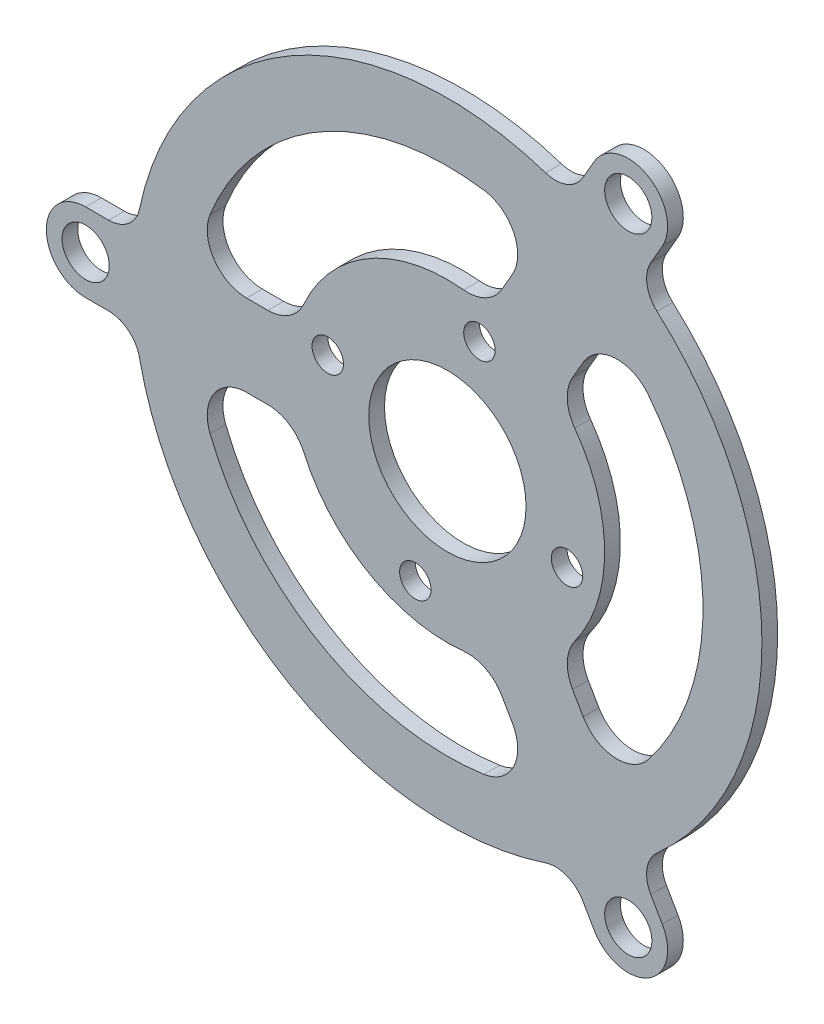
SolidWorks part; units mm, degrees
material "1060 Alloy"
ref_plane "Front Plane" through (0, 0, 0) normal (0, 0, 1) x (1, 0, 0)
ref_plane "Top Plane" through (0, 0, 0) normal (0, 1, 0) x (1, 0, 0)
ref_plane "Right Plane" through (0, 0, 0) normal (1, 0, 0) x (0, 0, -1)
sketch "Sketch1" plane through (0, 0, 0) normal (0, 0, 1) x (1, 0, 0)
  circle A0 centre (0, 0) radius 40
  dimension "D1" = 80
extrude "Boss-Extrude1" add sketch "Sketch1" along normal blind 2
ref_axis "Axis1" through (0, 0, 2) along (0, 0, -1)
sketch "Sketch4" plane through (0, 0, 0) normal (0, 0, -1) x (-1, 0, 0)
  line L0 (0, 0) -> (-40, 0) construction
  line L1 (0, 0) -> (20, 34.641) construction
  line L2 (0, 0) -> (-20, 34.641) construction
  line L3 (-20, 34.641) -> (-23, 39.8372) construction
  line L4 (-18.6699, 42.3372) -> (-15.513, 36.8693)
  line L5 (-27.3301, 37.3372) -> (-24.1733, 31.8693)
  line L6 (-27.3301, 37.3372) -> (-18.6699, 42.3372)
  line L7 (-24.1733, 31.8693) -> (-15.513, 36.8693)
  circle A0 centre (0, 0) radius 40 construction
  circle A1 centre (-23, 39.8372) radius 3
  arc A2 (-18.6699, 42.3372) -> (-27.3301, 37.3372) centre (-23, 39.8372) ccw
  circle M29 centre (0, 0) radius 40
  dimension "D3" = 6
  dimension "D5" = 2
  dimension "D1" = 120
  dimension "D2" = 60
  dimension "D4" = 6
extrude "Boss-Extrude3" add sketch "Sketch4" against normal blind 2 contours A1 L6 L5 L4 M29 | L6 A2 A1 region at (21.2054, 36.7287, 0) region at (19.5958, 41.9408, 0)
fillet "Fillet2" radius 4 2 edges at (24.1733, 31.8693, 1) (15.513, 36.8693, 1)
pattern_circular "CirPattern2" count 3 over 360 about axis through (0, 0, 2) along (0, 0, -1) of "Boss-Extrude3", "Fillet2"
sketch "Sketch5" plane through (0, 0, 0) normal (0, 0, -1) x (-1, 0, 0)
  circle A0 centre (0, 0) radius 10
  dimension "D1" = 20
extrude "Cut-Extrude1" cut sketch "Sketch5" against normal blind 8
sketch "Sketch6" plane through (0, 0, 0) normal (0, 0, -1) x (-1, 0, 0)
  line L0 (0, 0) -> (20, 0) construction
  line L1 (0, 0) -> (4.0764, -15.2133) construction
  line L2 (0, 0) -> (-14.8462, -25.7143) construction
  circle A0 centre (4.0764, -15.2133) radius 2
  circle A1 centre (0, 0) radius 20 construction
  dimension "D3" = 4
  dimension "D4" = 40
  dimension "D1" = 45
  dimension "D2" = 15.75
  dimension "D5" = 120
sketch "Sketch7" plane through (0, 0, 0) normal (0, 0, -1) x (-1, 0, 0)
  line L0 (0, 0) -> (54.9623, 0) construction
  line L1 (3, 5.1962) -> (32.0819, 5.1962)
  line L2 (-24.1148, 41.7681) -> (0, 0) construction
  line L3 (3, 5.1962) -> (-11.541, 30.3818)
  line L4 (0, 0) -> (3, 5.1962) construction
  circle A0 centre (0, 0) radius 20
  circle A1 centre (0, 0) radius 32.5
  circle A2 centre (0, 0) radius 6
  dimension "D2" = 12
  dimension "D4" = 40
  dimension "D5" = 65
  dimension "D1" = 120
  dimension "D3" = 60
extrude "Cut-Extrude3" cut sketch "Sketch7" against normal blind 15 contours L1 A1 L3 A0 region at (-11.8621, 20.5457, 0)
fillet "Fillet3" radius 5 4 edges at (-32.0819, 5.1962, 1) (-19.3132, 5.1962, 1) (5.1566, 19.3238, 1) (11.541, 30.3818, 1)
pattern_circular "CirPattern4" count 3 over 360 about axis through (0, 0, 2) along (0, 0, -1) of "Cut-Extrude3", "Fillet3" reverse direction yes
extrude "Cut-Extrude4" cut sketch "Sketch6" against normal blind 10
pattern_circular "CirPattern5" count 4 over 360 about axis through (0, 0, 8) along (0, 0, -1) of "Cut-Extrude4" reverse direction yes
